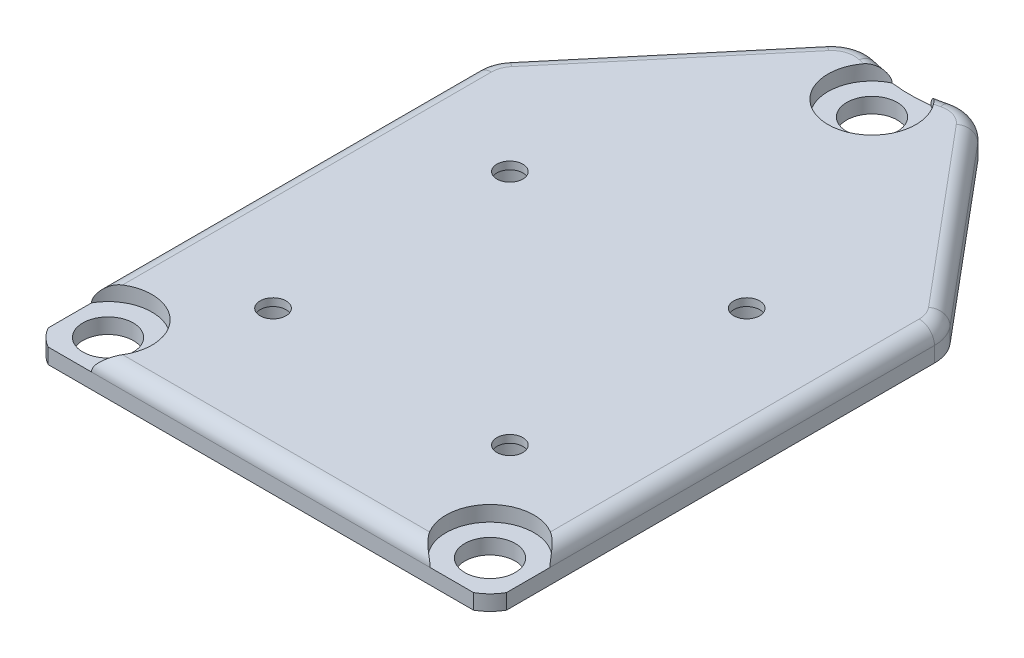
SolidWorks part; units mm, degrees
ref_plane "Front Plane" through (0, 0, 0) normal (0, 0, 1) x (1, 0, 0)
ref_plane "Top Plane" through (0, 0, 0) normal (0, 1, 0) x (1, 0, 0)
ref_plane "Right Plane" through (0, 0, 0) normal (1, 0, 0) x (0, 0, -1)
sketch "Sketch1" plane through (0, 0, 0) normal (0, 1, 0) x (1, 0, 0)
  line L0 (0, 0) -> (0, -72.4) construction
  circle A0 centre (0, -72.4) radius 6.3405 construction
  point P4 (25, -100)
  point P7 (-25, -100)
  point P17 (0, -25)
  dimension "D1" = 72.4
  dimension "D2" = 25
  dimension "D3" = 100
  dimension "D5" = 25
sketch "Sketch2" plane through (0, 0, 0) normal (0, 1, 0) x (1, 0, 0)
  line L0 (-30, -45) -> (-7.7214, -18.4494)
  line L6 (0, 0) -> (0, -72.4) construction
  line L7 (0, -75) -> (0, -52.0117) construction
  line L9 (-30, -105) -> (30, -105)
  line L10 (-30, -105) -> (-30, -45)
  line L12 (30, -105) -> (30, -45)
  line L13 (-30, -105) -> (30, -45) construction
  line L14 (-30, -45) -> (30, -105) construction
  line L15 (7.7214, -18.4494) -> (30, -45)
  arc A0 (-7.7214, -18.4494) -> (7.7214, -18.4494) centre (0, 0) ccw
  point P14 (0, -75)
  point P15 (0, -75)
  dimension "D5" = 220
  dimension "D6" = 220
  dimension "D2" = 20
  dimension "D1" = 25
  dimension "D3" = 60
  dimension "D4" = 60
extrude "Boss-Extrude1" add sketch "Sketch2" along normal blind 4 contours L10 L0 A0 L15 L12 L9
hole_wizard "Hole1" positions "Sketch3" profile "Sketch4" legacy end condition up to next
sketch "Sketch3" plane through (0, 4, 0) normal (0, 1, 0) x (1, 0, 0)
  point P4 (-25, -100)
  point P6 (25, -100)
  point P14 (0, -25)
sketch "Sketch4" plane through (-25, 4, 100) normal (1, 0, 0) x (0, 0, 1)
  line L0 (0, 0) -> (0, 4)
  line L1 (0, 4) -> (3.3, 4)
  line L3 (3.3, 4) -> (3.3, 2)
  line L4 (3.3, 2) -> (5.75, 2)
  line L5 (5.75, 2) -> (5.75, 0)
  line L7 (5.75, 0) -> (0, 0)
  line L11 (0, -6.35) -> (0, 107.95) construction
  dimension "Thru Hole Dia." = 6.6
  dimension "Thru Hole Depth" = 4
  dimension "C'Bore Dia." = 11.5
  dimension "C'Bore Depth" = 2
sketch "Sketch5" plane through (0, 4, 0) normal (0, 1, 0) x (1, 0, 0)
  line L0 (-30, -105) -> (-27.8395, -105) construction
  line L5 (-30, -102.8395) -> (-30, -105)
  line L6 (-30, -105) -> (-27.8395, -105)
  line L11 (0, -105) -> (0, -90.3325) construction
  line L12 (-22.1605, -105) -> (22.1605, -105) construction
  line L13 (30, -105) -> (27.8395, -105)
  line L14 (30, -102.8395) -> (30, -105)
  arc A0 (-30, -102.8395) -> (-27.8395, -105) centre (-25, -100) ccw
  arc A1 (30, -102.8395) -> (27.8395, -105) centre (25, -100) cw
extrude "Cut-Extrude3" cut sketch "Sketch5" against normal through all
sketch "Sketch6" plane through (0, 0, 0) normal (0, -1, 0) x (1, 0, 0)
  line L0 (0, 0) -> (0, 72.4) construction
  point P0 (-15.5, 56.9)
  point P5 (0, 72.4)
  point P8 (-15.5, 87.9)
  point P9 (15.5, 87.9)
  point P10 (15.5, 56.9)
  point P11 (0, 72.4)
  dimension "D1" = 15.5
  dimension "D2" = 15.5
  dimension "D3" = 4
hole_wizard "CBORE for M3 SHCS1" positions "Sketch7" profile "Sketch8" counterbore size "M3" standard "ANSI Metric" end condition through all
sketch "Sketch7" plane through (0, 0, 0) normal (0, -1, 0) x (-1, 0, 0)
  point P0 (-15.5, -56.9)
  point P3 (15.5, -56.9)
  point P6 (15.5, -87.9)
  point P9 (-15.5, -87.9)
sketch "Sketch8" plane through (15.5, 0, 56.9) normal (1, 0, 0) x (0, 0, -1)
  line L0 (0, 0) -> (0, 4)
  line L1 (0, 4) -> (1.7, 4)
  line L3 (1.7, 4) -> (1.7, 3)
  line L4 (1.7, 3) -> (3.25, 3)
  line L5 (3.25, 3) -> (3.25, 0)
  line L7 (3.25, 0) -> (0, 0)
  line L11 (0, -6.35) -> (0, 107.95) construction
  dimension "Thru Hole Dia." = 3.4
  dimension "Thru Hole Depth" = 4
  dimension "C'Bore Dia." = 6.5
  dimension "C'Bore Depth" = 3
fillet "Fillet4" radius 5 4 edges at (-30, 2, 45) (-7.7214, 2, 18.4494) (7.7214, 2, 18.4494) (30, 2, 45)
fillet "Fillet3" radius 2 11 edges at (30, 4, 71.9902) (0, 4, 105) (-30, 4, 71.9902) (-19.3624, 4, 32.3226) (-29.6985, 4, 45.1098) (-3.6995, 4, 19.6549) (-7.6079, 4, 19.4975) (29.6985, 4, 45.1098) (19.3624, 4, 32.3226) (7.6079, 4, 19.4975) (3.6995, 4, 19.6549)
